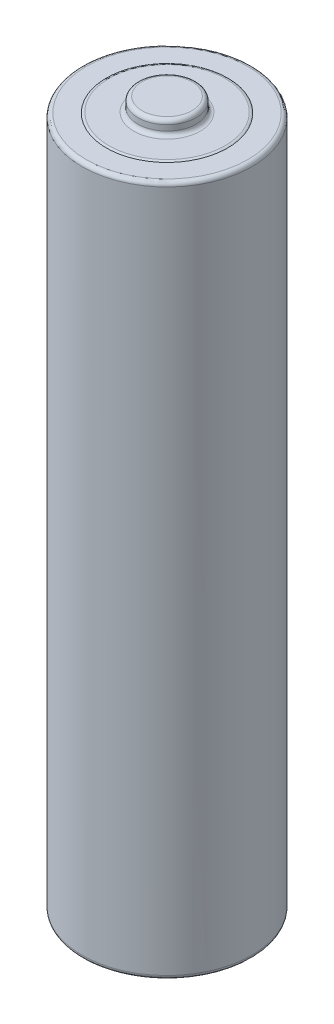
SolidWorks part; units mm, degrees
ref_plane "Front Plane" through (0, 0, 0) normal (0, 0, 1) x (1, 0, 0)
ref_plane "Top Plane" through (0, 0, 0) normal (0, 1, 0) x (1, 0, 0)
ref_plane "Right Plane" through (0, 0, 0) normal (1, 0, 0) x (0, 0, -1)
ref_axis "Battery Cell Cylinder Axis" through (0, -28.2802, 0) along (0, 1, 0)
sketch "Sketch1" plane through (0, 0, 0) normal (0, 0, 1) x (1, 0, 0)
  line L0 (0, 22.2) -> (0, -22.2) construction
  line L1 (-3.3, -22.2) -> (3.3, -22.2)
  line L2 (-5.25, -21.438) -> (-5.25, 21.3)
  line L3 (-5.25, 21.3) -> (-3.75, 21.3)
  line L4 (5.25, -21.438) -> (5.25, 21.3)
  line L6 (-1.8, 21.35) -> (-1.8, 22.2)
  line L7 (-1.8, 22.2) -> (1.8, 22.2)
  line L8 (1.8, 21.35) -> (1.8, 22.2)
  line L9 (5.25, -21.438) -> (3.3, -21.438)
  line L10 (3.3, -21.438) -> (3.3, -22.2)
  line L11 (-3.3, -21.438) -> (-3.3, -22.2)
  line L12 (-5.25, -21.438) -> (-3.3, -21.438)
  line L13 (-3.75, 21.3) -> (-3.75, 21.35)
  line L14 (-3.75, 21.35) -> (-1.8, 21.35)
  line L15 (3.75, 21.35) -> (3.75, 21.3)
  line L16 (1.8, 21.35) -> (3.75, 21.35)
  line L17 (3.75, 21.3) -> (5.25, 21.3)
  dimension "D1" = 10.5
  dimension "D2" = 44.4
  dimension "D3" = 0.9
  dimension "D4" = 3.6
  dimension "D5" = 0.762
  dimension "D6" = 6.6
  dimension "D7" = 1.5
  dimension "D8" = 0.85
ref_plane "+ Contact" through (0, 22.2, 0) normal (0, 1, 0) x (1, 0, 0)
ref_plane "- Contact" through (0, -22.2, 0) normal (0, 1, 0) x (1, 0, 0)
sketch "Sketch2" plane through (0, 0, 0) normal (0, 0, 1) x (1, 0, 0)
  line L4 (-3.3, -22.2) -> (3.3, -22.2)
  line L5 (5.25, -21.438) -> (5.25, 21.3)
  line L6 (-3.75, 21.3) -> (-5.25, 21.3)
  line L7 (-5.25, 21.3) -> (-5.25, -21.438)
  line L8 (0, -22.2) -> (3.3, -22.2)
  line L9 (5.25, -21.438) -> (5.25, 21.3)
  line L14 (0, 22.2) -> (0, -22.2) construction
  line L15 (0, 22.2) -> (0, -22.2)
  line L21 (3.3, -22.2) -> (3.3, -21.438)
  line L22 (3.3, -22.2) -> (3.3, -21.438)
  line L23 (3.3, -21.438) -> (5.25, -21.438)
  line L24 (3.3, -21.438) -> (5.25, -21.438)
  line L25 (-5.25, -21.438) -> (-3.3, -21.438)
  line L27 (-3.3, -21.438) -> (-3.3, -22.2)
  line L37 (5.25, 21.3) -> (3.75, 21.3)
  line L38 (5.25, 21.3) -> (3.75, 21.3)
  line L39 (3.75, 21.3) -> (3.75, 21.35)
  line L40 (3.75, 21.3) -> (3.75, 21.35)
  line L41 (3.75, 21.35) -> (1.8, 21.35)
  line L42 (3.75, 21.35) -> (1.8, 21.35)
  line L43 (1.8, 21.35) -> (1.8, 22.2)
  line L44 (1.8, 21.35) -> (1.8, 22.2)
  line L45 (1.8, 22.2) -> (-1.8, 22.2)
  line L46 (1.8, 22.2) -> (0, 22.2)
  line L47 (-1.8, 22.2) -> (-1.8, 21.35)
  line L49 (-1.8, 21.35) -> (-3.75, 21.35)
  line L51 (-3.75, 21.35) -> (-3.75, 21.3)
  dimension "D1" = 0
revolve "Revolve1" add sketch "Sketch2" angle 360 about axis through (0, -28.2802, 0) along (0, 1, 0)
fillet "Fillet1" radius 0.254 2 edges at (0, 21.3, -5.25) (0, -21.438, -5.25)
fillet "Fillet2" radius 0.254 5 edges at (0, -22.2, -3.3) (0, -21.438, -3.3) (0, 21.35, -3.75) (0, 21.35, -1.8) (0, 22.2, -1.8)
ref_axis "Axis1" [suppressed] through (0, 19.4074, 0) along (0, -1, 0)
